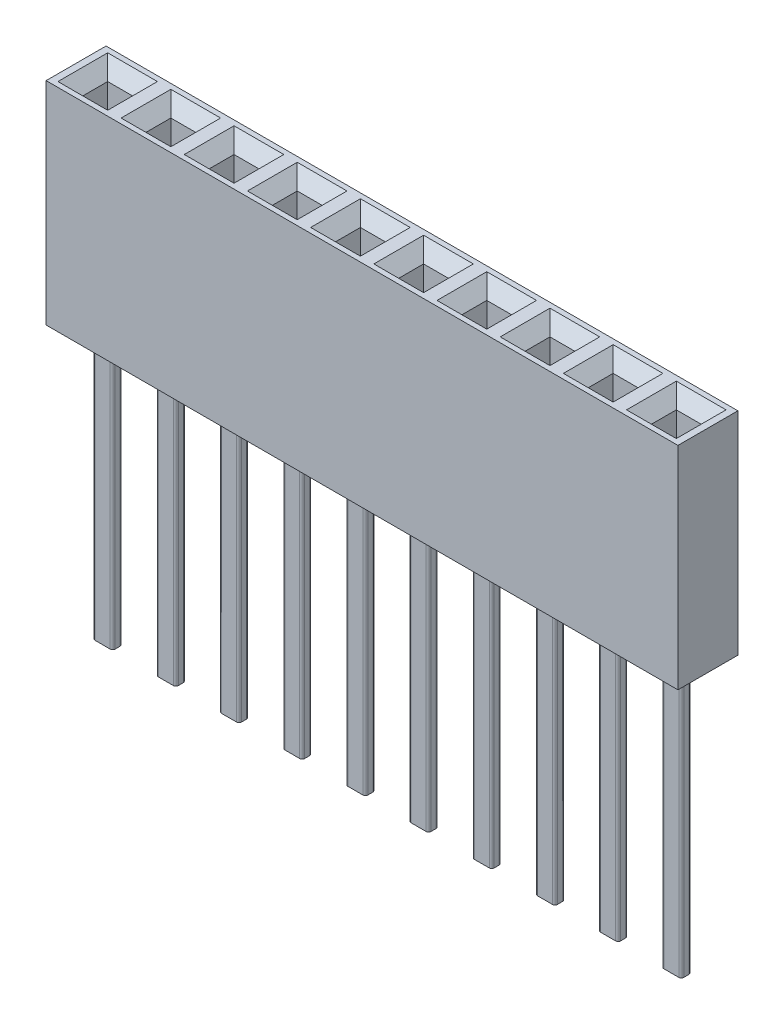
SolidWorks part; units mm, degrees
material "PA Type 6"
ref_plane "Front Plane" through (0, 0, 0) normal (0, 0, 1) x (1, 0, 0)
ref_plane "Top Plane" through (0, 0, 0) normal (0, 1, 0) x (1, 0, 0)
ref_plane "Right Plane" through (0, 0, 0) normal (1, 0, 0) x (0, 0, -1)
ref_plane "Plane1" through (0, -1.65, 0) normal (0, 1, 0) x (1, 0, 0)
sketch "Sketch2" plane through (0, 0, 0) normal (0, 1, 0) x (1, 0, 0)
  line L0 (0, -55) -> (0, 55) construction
  line L1 (-1.27, 1.205) -> (24.13, 1.205)
  line L2 (-1.27, 1.205) -> (-1.27, -1.205)
  line L3 (-1.27, -1.205) -> (24.13, -1.205)
  line L4 (24.13, 1.205) -> (24.13, -1.205)
  line L5 (-55, 0) -> (55, 0) construction
  dimension "D1" = 25.4
  dimension "D2" = 1.27
  dimension "D3" = 2.41
  dimension "D4" = 1.205
extrude "Boss-Extrude1" add sketch "Sketch2" along normal blind 8.51
sketch "Sketch5" plane through (0, 8.51, 0) normal (0, 1, 0) x (1, 0, 0)
  line L0 (-55, 0) -> (55, 0) construction
  line L1 (0.5, 0.5) -> (-0.5, 0.5)
  line L2 (0.5, 0.5) -> (0.5, -0.5)
  line L3 (0.5, -0.5) -> (-0.5, -0.5)
  line L4 (-0.5, 0.5) -> (-0.5, -0.5)
  line L5 (0, -55) -> (0, 55) construction
  dimension "D1" = 0.5
  dimension "D2" = 1
  dimension "D3" = 0.5
extrude "Cut-Extrude1" cut sketch "Sketch5" against normal blind 5
chamfer "Chamfer1" distance 0.5 angle 45 4 edges at (-0.5, 8.51, 0) (0, 8.51, 0.5) (0.5, 8.51, 0) (0, 8.51, -0.5)
pattern_linear "LPattern3" count 10 spacing 2.54 along (1, 0, 0) of "Chamfer1", "Cut-Extrude1"
sketch "Sketch8" plane through (0, 0, 0) normal (0, 1, 0) x (1, 0, 0)
  line L0 (0, -1.3255) -> (0, 1.3255) construction
  line L1 (-0.3, -0.2) -> (0.3, -0.2)
  line L2 (-0.4, -0.1) -> (-0.4, 0.1)
  line L3 (-0.3, 0.2) -> (0.3, 0.2)
  line L4 (0.4, -0.1) -> (0.4, 0.1)
  line L5 (-4.6805, 0) -> (4.6805, 0) construction
  arc A0 (-0.3, -0.2) -> (-0.4, -0.1) centre (-0.3, -0.1) cw
  arc A1 (0.3, -0.2) -> (0.4, -0.1) centre (0.3, -0.1) ccw
  arc A2 (0.3, 0.2) -> (0.4, 0.1) centre (0.3, 0.1) cw
  arc A3 (-0.4, 0.1) -> (-0.3, 0.2) centre (-0.3, 0.1) cw
  point P10 (-0.4, -0.2)
  point P13 (0.4, -0.2)
  point P16 (0.4, 0.2)
  dimension "D5" = 0.1
  dimension "D1" = 0.4
  dimension "D2" = 0.8
  dimension "D3" = 0.4
  dimension "D4" = 0.2
extrude "Boss-Extrude2" add sketch "Sketch8" against normal blind 11
sketch "Sketch10" plane through (0, -1.65, 0) normal (0, 1, 0) x (1, 0, 0)
  line L0 (0, -0.25) -> (0, 0.25) construction
  line L1 (0, -1.3255) -> (0, 1.3255) construction
  line L2 (-0.75, -0.25) -> (-0.75, 0.25)
  line L3 (0.75, -0.25) -> (0.75, 0.25)
  line L4 (-5.7805, 0) -> (5.7805, 0) construction
  arc A0 (-0.75, -0.25) -> (0.75, -0.25) centre (0, -0.25) ccw
  arc A1 (0.75, 0.25) -> (-0.75, 0.25) centre (0, 0.25) ccw
  point P5 (0, 0)
  dimension "D1" = 1.5
  dimension "D2" = 0.5
extrude "Boss-Extrude3" [suppressed] add sketch "Sketch10" along normal blind 0.1
fillet "Fillet2" [suppressed] radius 0.4
pattern_linear "LPattern1" count 10 spacing 2.54 along (1, 0, 0) of "Boss-Extrude2", "Fillet2", "Boss-Extrude3"
ref_axis "Axis1" through (0, -2.5255, 0) along (0, 1, 0)
equation "\"D1@Sketch2\"=2.54 * 10"
